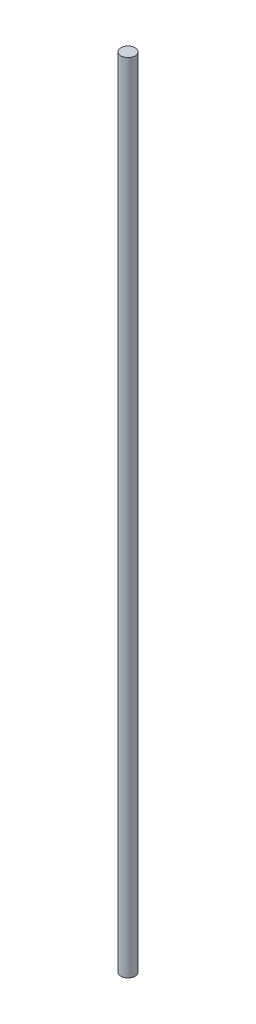
SolidWorks part; units mm, degrees
ref_plane "Front Plane" through (0, 0, 0) normal (0, 0, 1) x (1, 0, 0)
ref_plane "Top Plane" through (0, 0, 0) normal (0, 1, 0) x (1, 0, 0)
ref_plane "Right Plane" through (0, 0, 0) normal (1, 0, 0) x (0, 0, -1)
sketch "Sketch1" plane through (0, 0, 0) normal (0, 1, 0) x (1, 0, 0)
  circle A0 centre (0, 0) radius 4
extrude "Boss-Extrude1" add sketch "Sketch1" along normal blind 450
